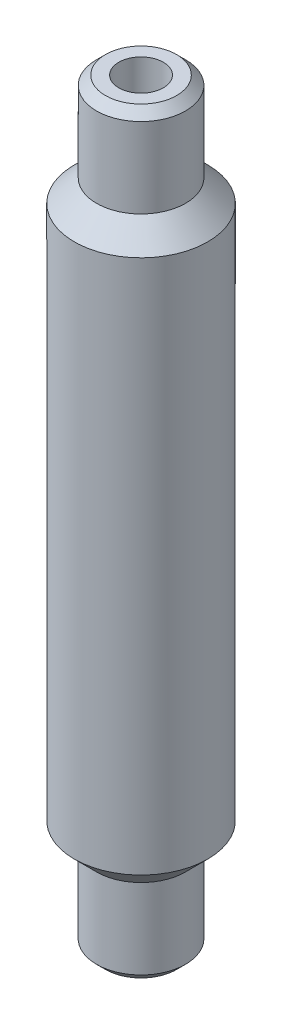
SolidWorks part; units mm, degrees
ref_plane "Front Plane" through (0, 0, 0) normal (0, 0, 1) x (1, 0, 0)
ref_plane "Top Plane" through (0, 0, 0) normal (0, 1, 0) x (1, 0, 0)
ref_plane "Right Plane" through (0, 0, 0) normal (1, 0, 0) x (0, 0, -1)
sketch "Sketch1" plane through (0, 0, 0) normal (0, 1, 0) x (1, 0, 0)
  circle A0 centre (0, 0) radius 9.525
  circle A1 centre (0, 0) radius 3.175
  circle A2 centre (0, 0) radius 6.35
  dimension "D1" = 19.05
  dimension "D2" = 6.35
  dimension "D3" = 12.7
extrude "Boss-Extrude1" add sketch "Sketch1" along normal blind 82.6973 contours A0 A1 | A2 A1 region at (-9.2556, 0, 0) region at (-6.1704, 0, 0)
chamfer "Chamfer1" distance 3.175 angle 45 2 edges at (0, 0, 9.525) (0, 82.6973, 9.525)
extrude "Boss-Extrude2" add sketch "Sketch1<3>" against normal blind 12.7 contours A2 A1 region at (-6.1704, 0, 0)
sketch "Sketch1<3>" plane through (0, 0, 0) normal (0, 1, 0) x (1, 0, 0) same geometry as "Sketch1"
extrude "Boss-Extrude3" add sketch "Sketch1<4>" along normal blind 12.7 from surface contours A2 A1 region at (-6.1704, 0, 0) starting at face at (0, 82.6973, 6.35)
sketch "Sketch1<4>" plane through (0, 0, 0) normal (0, 1, 0) x (1, 0, 0) same geometry as "Sketch1"
chamfer "Chamfer2" distance 1.27 angle 45 2 edges at (0, 95.3973, 6.35) (0, -12.7, 6.35)
